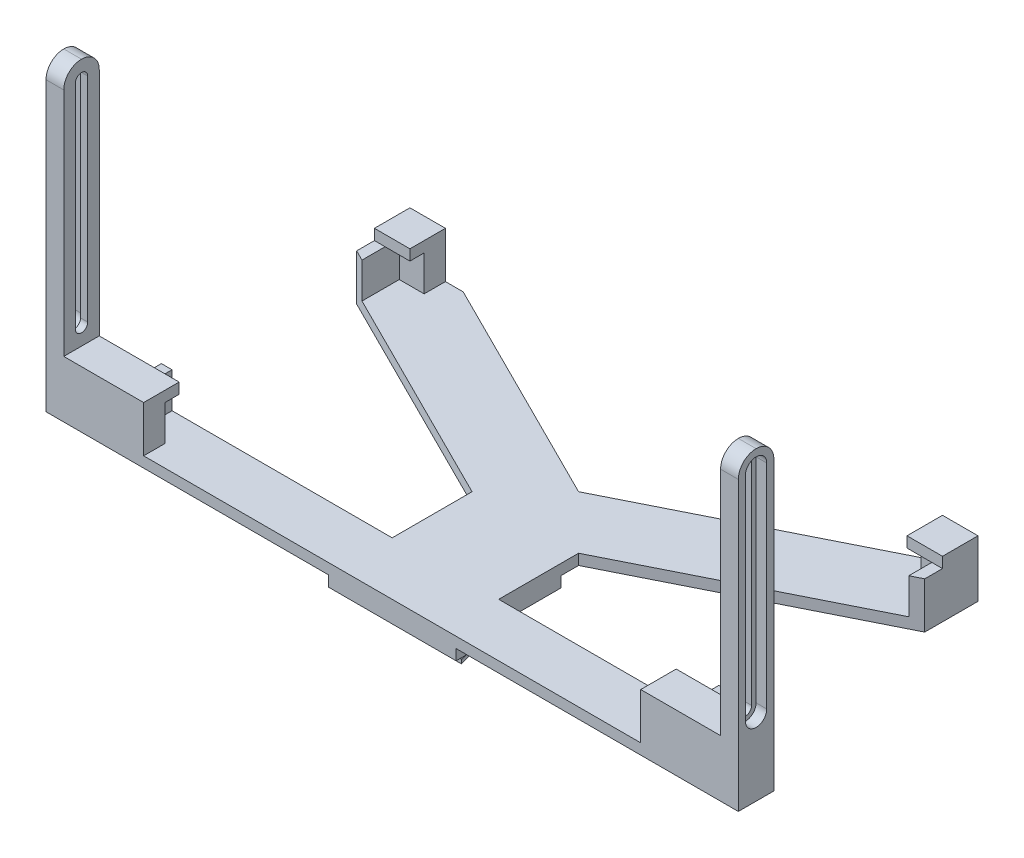
SolidWorks part; units mm, degrees
ref_plane "前视基准面" through (0, 0, 0) normal (0, 0, 1) x (1, 0, 0)
ref_plane "上视基准面" through (0, 0, 0) normal (0, 1, 0) x (1, 0, 0)
ref_plane "右视基准面" through (0, 0, 0) normal (1, 0, 0) x (0, 0, -1)
sketch "草图1" plane through (0, 0, 0) normal (0, 1, 0) x (1, 0, 0)
  line L0 (-8, 28.5) -> (8, 28.5)
  line L1 (8, 28.5) -> (15.5, 0)
  line L2 (15.5, 0) -> (-15.5, 0)
  line L3 (-15.5, 0) -> (-8, 28.5)
  line L4 (0, -32.0604) -> (0, 1570.9599) construction
  point P6 (0, 28.5)
  point P8 (0, 0)
  dimension "D1" = 31
  dimension "D2" = 16
  dimension "D3" = 28.5
extrude "凸台-拉伸1" add sketch "草图1" along normal blind 4
fillet "圆角1" radius 3 2 edges at (11.75, 4, -14.25) (-11.75, 4, -14.25) profile chamfer
sketch "草图2" plane through (0, 4, 0) normal (0, 1, 0) x (1, 0, 0)
  line L0 (-4.8979, 28.5) -> (-9.3158, 23.5)
  line L1 (-15.5, 0) -> (-8, 28.5) construction
  line L2 (-9.3158, 23.5) -> (-9.3158, 28.5)
  line L3 (-9.3158, 28.5) -> (-4.8979, 28.5)
  line L4 (0, -1000) -> (0, 49000) construction
  line L5 (-12.3979, 0) -> (12.3979, 0) construction
  line L6 (9.3158, 28.5) -> (4.8979, 28.5)
  line L7 (9.3158, 23.5) -> (9.3158, 28.5)
  line L8 (4.8979, 28.5) -> (9.3158, 23.5)
  point P11 (0, 0)
  dimension "D1" = 5
extrude "切除-拉伸1" cut sketch "草图2" against normal through all
sketch "草图3" plane through (0, 4, 0) normal (0, 1, 0) x (1, 0, 0)
  line L0 (0, 9.5574) -> (0, 0) construction
  line L1 (-4.8979, 28.5) -> (-12.3979, 0) construction
  circle A0 centre (0, 9.5574) radius 9.5574
extrude "凸台-拉伸2" add sketch "草图3" along normal blind 3 contours A0
sketch "草图5" plane through (0, 0, 0) normal (0, -1, 0) x (1, 0, 0)
  line L0 (-7.5, -24) -> (7.5, -24)
  line L1 (7.5, -24) -> (7.5, -22)
  line L2 (7.5, -22) -> (6, -22)
  line L3 (6, -22) -> (6, -4)
  line L4 (6, -4) -> (-6, -4)
  line L5 (-6, -4) -> (-6, -22)
  line L6 (-6, -22) -> (-7.5, -22)
  line L7 (-7.5, -22) -> (-7.5, -24)
  line L8 (-6, -22) -> (6, -22) construction
  line L9 (0, -1000) -> (0, 49000) construction
  line L10 (-15.5, 0) -> (15.5, 0) construction
  point P9 (0, -4)
  point P12 (0, -24)
  dimension "D1" = 12
  dimension "D2" = 15
  dimension "D3" = 4
  dimension "D4" = 2
  dimension "D5" = 20
extrude "切除-拉伸2" cut sketch "草图5" against normal blind 2
sketch "草图7" plane through (0, 7, 0) normal (0, 1, 0) x (1, 0, 0)
  circle A0 centre (0, 9.5574) radius 2
  dimension "D1" = 4
extrude "切除-拉伸3" cut sketch "草图7" against normal through all
sketch "草图8" plane through (0, 0, 0) normal (1, 0, 0) x (0, 0, -1)
  line L0 (7.5574, 5) -> (5.5574, 3)
  line L1 (7.5574, 7) -> (7.5574, 2) construction
  line L3 (5.5574, 3) -> (9.5574, 3) construction
  line L4 (7.5574, 5) -> (9.5574, 5)
  line L5 (9.5574, -993) -> (9.5574, 49007) construction
  line L6 (19.1147, 7) -> (0, 7) construction
  line L7 (11.5574, 7) -> (7.5574, 7) construction
  line L8 (22, 2) -> (4, 2) construction
  line L9 (9.5574, 2) -> (9.5574, 5)
  line L10 (5.5574, 3) -> (5.5574, 2)
  line L11 (5.5574, 2) -> (9.5574, 2)
  point P13 (9.5574, 7)
  dimension "D1" = 2
  dimension "D2" = 4
  dimension "D3" = 1
revolve "切除-旋转1" cut sketch "草图8" angle 360 about L5
fillet "圆角2" radius 1 4 edges at (-7.5, 1, -22) (-7.5, 1, -24) (7.5, 1, -24) (7.5, 1, -22)
sketch "草图9" plane through (0, 4, 0) normal (0, 1, 0) x (1, 0, 0)
  line L0 (-18, -4) -> (18, -4)
  line L1 (-12.3979, 0) -> (0, 0) construction
  line L2 (-18, -4) -> (-18, 28.5)
  line L3 (-18, 28.5) -> (18, 28.5)
  line L4 (18, 28.5) -> (18, -4)
  line L5 (4.8979, 28.5) -> (-4.8979, 28.5) construction
  circle A0 centre (0, 9.5574) radius 9.5574
  circle A1 centre (0, 9.5574) radius 9.5574 construction
  point P4 (0, -4)
  dimension "D1" = 4
  dimension "D2" = 36
extrude "凸台-拉伸4" add sketch "草图9" along normal up to surface (3 mm away) up to face at (0, 7, -7.5574)
sketch "草图10" plane through (0, 7, 0) normal (0, 1, 0) x (1, 0, 0)
  line L1 (-80, -4) -> (80, -4)
  line L2 (-80, -4) -> (-80, 81)
  line L3 (-80, 81) -> (80, 81)
  line L4 (80, -4) -> (80, 81)
  line L5 (-80, -4) -> (80, 81) construction
  line L6 (-80, 81) -> (80, -4) construction
  line L7 (0, 0) -> (0, 38.5) construction
  line L8 (-18, -4) -> (18, -4) construction
  point P0 (0, 38.5)
  dimension "D1" = 160
  dimension "D2" = 85
extrude "凸台-拉伸5" add sketch "草图10" along normal blind 3
sketch "草图11" plane through (0, 10, 0) normal (0, 1, 0) x (1, 0, 0)
  line L0 (-80, -4) -> (80, -4) construction
  line L1 (-80, 81) -> (-77, 81)
  line L2 (-80, 81) -> (-80, -4)
  line L3 (-80, -4) -> (-77, -4)
  line L4 (-77, 81) -> (-77, -4)
  line L6 (80, 81) -> (77, 81)
  line L7 (80, 81) -> (80, -4)
  line L8 (80, -4) -> (77, -4)
  line L9 (77, 81) -> (77, -4)
  dimension "D1" = 3
  dimension "D2" = 3
extrude "凸台-拉伸6" add sketch "草图11" along normal blind 10
sketch "草图12" plane through (0, 10, 0) normal (0, 1, 0) x (1, 0, 0)
  line L0 (-80, 81) -> (-80, -4) construction
  line L1 (-80, 81) -> (-70, 81)
  line L2 (-80, 81) -> (-80, 75)
  line L3 (-80, 75) -> (-70, 75)
  line L4 (-70, 81) -> (-70, 75)
  line L5 (80, 81) -> (70, 81)
  line L6 (80, 81) -> (80, 75)
  line L7 (80, 75) -> (70, 75)
  line L8 (70, 81) -> (70, 75)
  line L9 (80, -4) -> (70, -4)
  line L10 (80, -4) -> (80, 2)
  line L11 (80, 2) -> (70, 2)
  line L12 (70, -4) -> (70, 2)
  line L13 (-80, -4) -> (-70, -4)
  line L14 (-80, -4) -> (-80, 2)
  line L15 (-80, 2) -> (-70, 2)
  line L16 (-70, -4) -> (-70, 2)
  line L17 (-70, 75) -> (70, 75) construction
  line L18 (-70, 75) -> (-70, 2) construction
  line L19 (-70, 2) -> (70, 2) construction
  line L20 (70, 75) -> (70, 2) construction
  line L21 (80, -4) -> (80, 81) construction
  dimension "D1" = 6
  dimension "D2" = 6
  dimension "D3" = 10
  dimension "D4" = 10
extrude "凸台-拉伸7" add sketch "草图12" along normal blind 10
sketch "草图13" plane through (0, 20, 0) normal (0, 1, 0) x (1, 0, 0)
  line L0 (-70, 81) -> (-80, 81) construction
  line L9 (-70, 71) -> (-80, 71)
  line L10 (-70, 71) -> (-70, 81)
  line L11 (-70, 81) -> (-80, 81)
  line L12 (-80, 71) -> (-80, 81)
  line L13 (-70, 71) -> (-80, 81) construction
  line L14 (-70, 81) -> (-80, 71) construction
  line L15 (-80, 81) -> (-80, -4) construction
  line L16 (-70, -4) -> (-70, 2) construction
  line L17 (-70, 6) -> (-80, 6)
  line L18 (-70, 6) -> (-70, -4)
  line L19 (-70, -4) -> (-80, -4)
  line L20 (-80, 6) -> (-80, -4)
  line L21 (-70, 6) -> (-80, -4) construction
  line L22 (-70, -4) -> (-80, 6) construction
  line L23 (70, 71) -> (80, 71)
  line L24 (70, 71) -> (70, 81)
  line L25 (70, 81) -> (80, 81)
  line L26 (80, 71) -> (80, 81)
  line L27 (70, 71) -> (80, 81) construction
  line L28 (70, 81) -> (80, 71) construction
  line L29 (70, 6) -> (80, 6)
  line L30 (70, 6) -> (70, -4)
  line L31 (70, -4) -> (80, -4)
  line L32 (80, 6) -> (80, -4)
  line L33 (70, 6) -> (80, -4) construction
  line L34 (70, -4) -> (80, 6) construction
  line L35 (70, 2) -> (70, -4) construction
  line L36 (70, 81) -> (70, 75) construction
  line L39 (-70, 75) -> (-70, 81) construction
  point P0 (-75, 76)
  point P14 (-75, 1)
  point P21 (75, 76)
  point P28 (75, 1)
extrude "凸台-拉伸8" add sketch "草图13" along normal blind 3
sketch "草图14" plane through (-80, 0, 0) normal (-1, 0, 0) x (0, 0, 1)
  line L0 (14.1903, 14.4943) -> (37.8859, 46.7204)
  line L1 (37.8859, 46.7204) -> (-50.1764, 168.1495)
  line L2 (17.1092, 75.3694) -> (-45.4198, 55.1366)
  line L3 (-45.4198, 55.1366) -> (-43.0956, 17.5376)
  dimension "D1" = 40
  dimension "D2" = 37.6707
  dimension "D3" = 150
  dimension "D4" = 65.7209
  dimension "D5" = 107.723
  dimension "D6" = 35.3897
sketch "草图15" plane through (-80, 0, 0) normal (-1, 0, 0) x (0, 0, 1)
  line L0 (4, 7) -> (4, 23)
  line L1 (4, 23) -> (-6, 23)
  line L2 (-6, 23) -> (-6, 7)
  line L5 (-6, 7) -> (4, 7)
  dimension "D1" = 10
extrude "凸台-拉伸10" add sketch "草图15" along normal blind 12.5 contours L2 L5 L0 L1
sketch "草图17" plane through (-92.5, 0, 0) normal (-1, 0, 0) x (0, 0, 1)
  line L0 (-6, 7) -> (4, 7)
  line L1 (4, 7) -> (4, 93)
  line L2 (4, 93) -> (-6, 93)
  line L3 (-6, 93) -> (-6, 7)
  line L4 (-6, 23) -> (4, 23) construction
  dimension "D1" = 70
extrude "凸台-拉伸11" add sketch "草图17" along normal blind 5
sketch "草图19" plane through (-92.5, 0, 0) normal (1, 0, 0) x (0, 0, -1)
  line L0 (1, 88) -> (1, 28) construction
  line L1 (2.75, 88) -> (2.75, 28)
  line L2 (-0.75, 88) -> (-0.75, 28)
  line L3 (1, 88) -> (1, 93) construction
  line L4 (-4, 93) -> (6, 93) construction
  line L6 (-4, 23) -> (6, 23) construction
  arc A0 (2.75, 88) -> (-0.75, 88) centre (1, 88) ccw
  arc A1 (-0.75, 28) -> (2.75, 28) centre (1, 28) ccw
  point P2 (1, 58)
  dimension "D1" = 3.5
  dimension "D2" = 5
  dimension "D3" = 5
extrude "切除-拉伸5" cut sketch "草图19" against normal through all and the other way through all
sketch "草图20" plane through (-97.5, 0, 0) normal (-1, 0, 0) x (0, 0, 1)
  line L0 (-1, 88) -> (-1, 28) construction
  line L1 (2, 88) -> (2, 28)
  line L2 (-4, 88) -> (-4, 28)
  arc A0 (2, 88) -> (-4, 88) centre (-1, 88) ccw
  arc A1 (-4, 28) -> (2, 28) centre (-1, 28) ccw
  point P4 (-1, 58)
  dimension "D1" = 6
extrude "切除-拉伸6" cut sketch "草图20" against normal blind 3
fillet "圆角3" radius 5 2 edges at (-95, 93, 4) (-95, 93, -6)
mirror "镜向2" about plane through (0, 0, 0) normal (1, 0, 0) of "凸台-拉伸10", "凸台-拉伸11", "切除-拉伸5", "切除-拉伸6", "圆角3"
sketch "草图21" plane through (0, 20, 0) normal (0, 1, 0) x (1, 0, 0)
  line L4 (-920, 38.5) -> (49080, 38.5) construction
  line L5 (80, 6) -> (80, 71) construction
  line L7 (0, -1000) -> (0, 49000) construction
  line L17 (-65, 81) -> (65, 81)
  line L30 (70, 81) -> (-70, 81) construction
  line L31 (65, 81) -> (0, 48.5)
  line L32 (0, 48.5) -> (-65, 81)
  line L33 (-80, 66) -> (-15, 33.5)
  line L34 (-80, 71) -> (-80, 6) construction
  line L35 (-15, 33.5) -> (-15, 11)
  line L36 (-15, 11) -> (-80, 11)
  line L37 (-80, 11) -> (-80, 66)
  line L38 (-70, 75) -> (-70, 81) construction
  line L39 (-80, 71) -> (-70, 71) construction
  line L40 (15, 11) -> (80, 11)
  line L41 (15, 33.5) -> (15, 11)
  line L42 (80, 66) -> (15, 33.5)
  line L43 (80, 11) -> (80, 66)
  line L44 (-15, 33.5) -> (0, 48.5) construction
  line L45 (15, 33.5) -> (0, 48.5) construction
  point P10 (80, 38.5)
  point P18 (0, 51.6433)
  point P20 (0, 0)
  point P21 (-17.2824, 32.3277)
  dimension "D1" = 5
  dimension "D2" = 5
  dimension "D3" = 5
extrude "切除-拉伸7" cut sketch "草图21" against normal through all
equation "\"length\"= 150"
equation "\"width\"= 75"
equation "\"thick\"= 10"
equation "\"D1@草图10\" = \"length\" + 10"
equation "\"D2@草图10\"= \"width\" + 10"
equation "\"D1@凸台-拉伸6\"=\"thick\""
equation "\"D1@凸台-拉伸7\"=\"thick\""
